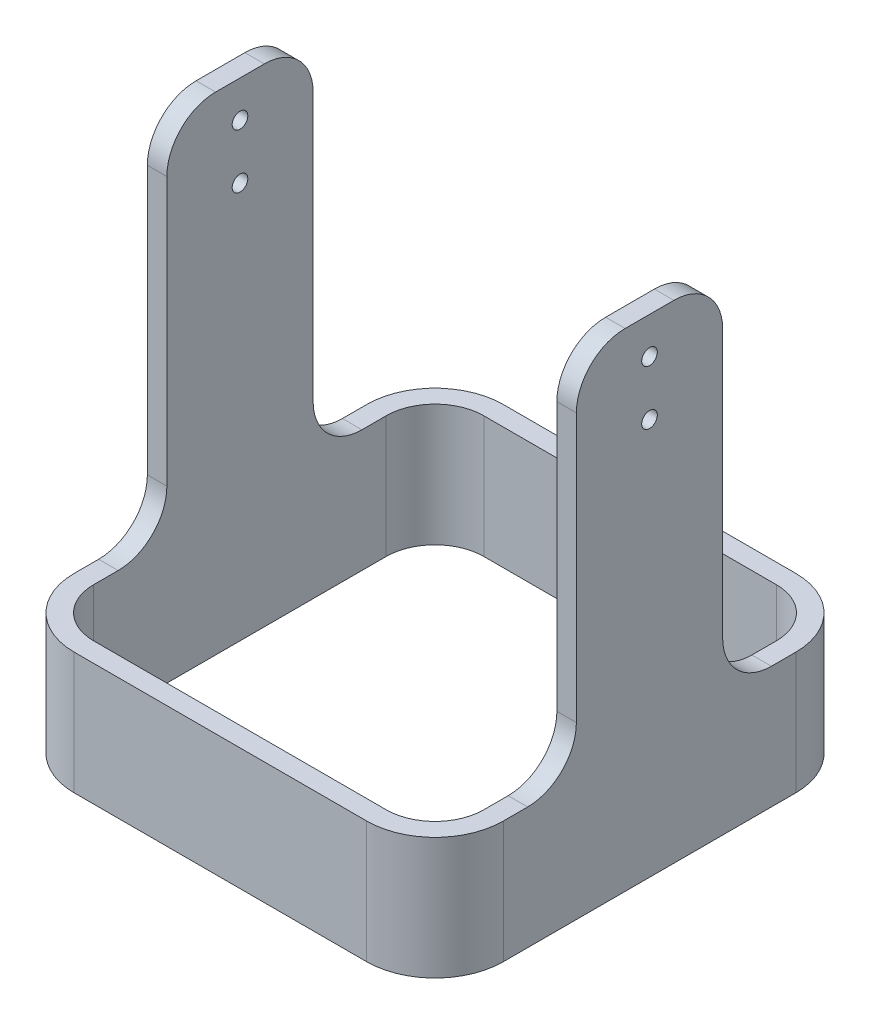
SolidWorks part; units mm, degrees
ref_plane "Plan de face" through (0, 0, 0) normal (0, 0, 1) x (1, 0, 0)
ref_plane "Plan de dessus" through (0, 0, 0) normal (0, 1, 0) x (1, 0, 0)
ref_plane "Plan de droite" through (0, 0, 0) normal (1, 0, 0) x (0, 0, -1)
sketch "Esquisse1" plane through (0, 0, 0) normal (0, 1, 0) x (1, 0, 0)
  line L1 (-88, -88) -> (88, -88)
  line L2 (-88, -88) -> (-88, 88)
  line L3 (-88, 88) -> (88, 88)
  line L4 (88, -88) -> (88, 88)
  line L5 (-88, -88) -> (88, 88) construction
  line L6 (-88, 88) -> (88, -88) construction
  line L7 (-80, -80) -> (80, -80)
  line L8 (-80, -80) -> (-80, 80)
  line L9 (-80, 80) -> (80, 80)
  line L10 (80, -80) -> (80, 80)
  line L11 (-80, -80) -> (80, 80) construction
  line L12 (-80, 80) -> (80, -80) construction
  point P0 (0, 0)
  point P6 (0, 0)
  dimension "D1" = 8
  dimension "D2" = 160
extrude "Boss.-Extru.1" add sketch "Esquisse1" along normal blind 50
sketch "Esquisse2" plane through (0, 50, 0) normal (0, 1, 0) x (1, 0, 0)
  line L0 (-88, 88) -> (-88, -88) construction
  line L1 (-88, -30) -> (-80, -30)
  line L2 (-88, -30) -> (-88, 30)
  line L3 (-88, 30) -> (-80, 30)
  line L4 (-80, -30) -> (-80, 30)
  line L5 (-80, 80) -> (-80, -80) construction
  line L6 (0, 0) -> (-80, 0) construction
  dimension "D1" = 60
extrude "Boss.-Extru.2" add sketch "Esquisse2" along normal blind 150
mirror "Symétrie1" about plane through (0, 0, 0) normal (1, 0, 0) of "Boss.-Extru.2"
sketch "Esquisse3" plane through (-88, 0, 0) normal (-1, 0, 0) x (0, 0, 1)
  line L0 (0, 200) -> (0, 185) construction
  line L1 (-30, 200) -> (30, 200) construction
  line L2 (0, 185) -> (0, 162.65) construction
  circle A0 centre (0, 185) radius 3.2
  circle A1 centre (0, 162.65) radius 3.2
  dimension "D3" = 6.4
  dimension "D1" = 15
  dimension "D2" = 22.35
extrude "Enlèv. mat.-Extru.1" cut sketch "Esquisse3" against normal through all
fillet "Congé1" radius 20 12 edges at (-80, 25, 80) (80, 25, 80) (80, 25, -80) (-80, 25, -80) (84, 50, 30) (84, 50, -30) (-84, 50, -30) (-84, 50, 30) (84, 200, -30) (84, 200, 30) (-84, 200, -30) (-84, 200, 30)
fillet "Congé2" radius 28 4 edges at (88, 25, -88) (88, 25, 88) (-88, 25, -88) (-88, 25, 88)
